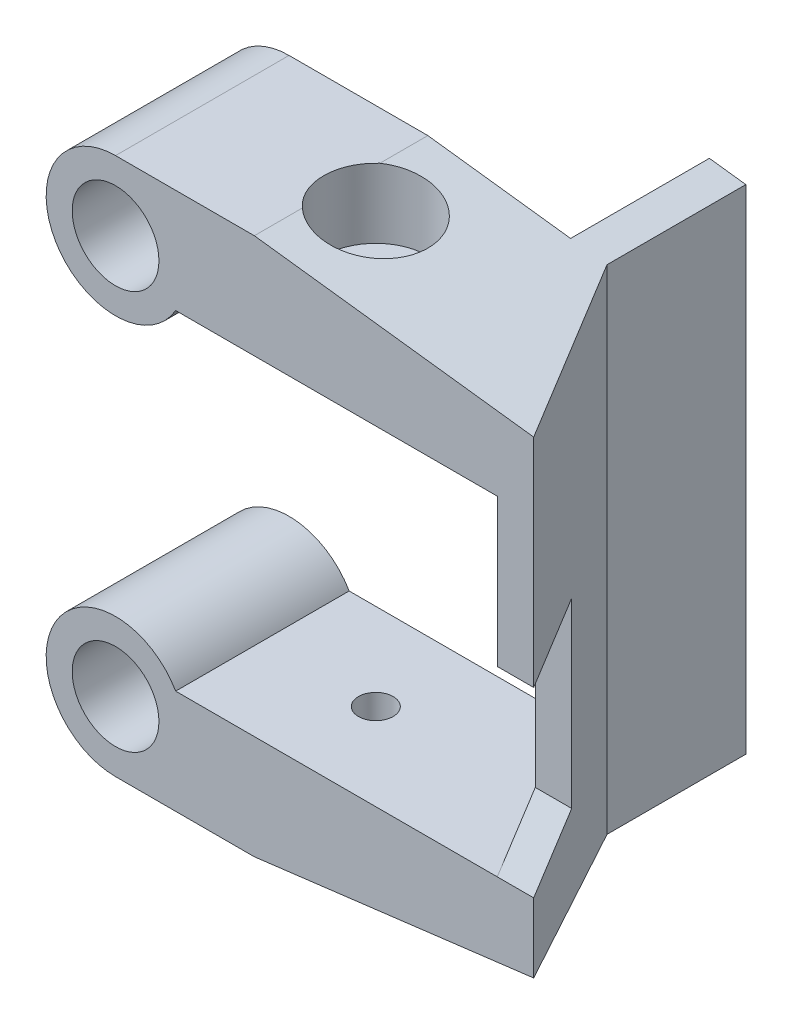
SolidWorks part; units mm, degrees
ref_plane "Alzado" through (0, 0, 0) normal (0, 0, 1) x (1, 0, 0)
ref_plane "Planta" through (0, 0, 0) normal (0, 1, 0) x (1, 0, 0)
ref_plane "Vista lateral" through (0, 0, 0) normal (1, 0, 0) x (0, 0, -1)
sketch "Croquis1" plane through (0, 0, 0) normal (0, 0, 1) x (1, 0, 0)
  line L0 (0, 2.5) -> (0, 3.5) construction
  line L1 (0, 3.5) -> (1.9365, 3.5) construction
  line L2 (3.4641, 3.5) -> (22, 3.5)
  line L3 (22, 3.5) -> (22, -0.5)
  line L4 (22, -0.5) -> (6, -0.5)
  line L7 (22, 3.5) -> (22, 22.5) construction
  line L8 (22, 22.5) -> (-6, 22.5) construction
  line L9 (0, 3.5) -> (0, 1.5) construction
  line L10 (0, -2.5) -> (6, -2.5)
  line L11 (6, -2.5) -> (6, -0.5)
  circle A3 centre (0, 1.5) radius 2.5
  arc A4 (3.4641, 3.5) -> (0, -2.5) centre (0, 1.5) ccw
  dimension "D1" = 6
  dimension "D2" = 2
  dimension "D7" = 5
  dimension "D8" = 4
  dimension "D3" = 1
  dimension "D4" = 22
  dimension "D5" = 4
  dimension "D6" = 19
extrude "Saliente-Extruir1" add sketch "Croquis1" along normal blind 10
sketch "Croquis2" plane through (0, -0.5, 0) normal (0, -1, 0) x (1, 0, 0)
  line L0 (22, 10) -> (16.2265, 0)
  line L1 (6, 0) -> (22, 0) construction
  line L2 (16.2265, 0) -> (22, 0)
  line L3 (22, 0) -> (22, 10)
  circle A0 centre (10, 5) radius 1
  dimension "D2" = 12
  dimension "D1" = 30
extrude "Cortar-Extruir1" cut sketch "Croquis2" against normal up to vertex (4 mm away) up to point (3.4641, 3.5, 10)
sketch "Croquis3" plane through (0, -0.5, 0) normal (0, -1, 0) x (1, 0, 0)
  circle A0 centre (10, 5) radius 3
  dimension "D1" = 6
extrude "Cortar-Extruir2" cut sketch "Croquis3" against normal blind 2
sketch "Croquis4" plane through (0, -0.5, 0) normal (0, -1, 0) x (1, 0, 0)
  line L0 (22, 10) -> (24.1, 10)
  line L1 (24.1, 10) -> (18.3265, 0)
  line L2 (18.3265, 0) -> (16.2265, 0)
  line L3 (22, 10) -> (16.2265, 0)
  dimension "D1" = 2.1
  dimension "D2" = 2.1
extrude "Saliente-Extruir2" add sketch "Croquis4" against normal blind 13.5
sketch "Croquis6" plane through (0, -0.5, 0) normal (0, -1, 0) x (1, 0, 0)
  line L0 (6, 10) -> (6, 0)
  line L1 (6, 0) -> (18.3265, 0)
  line L2 (18.3265, 0) -> (24.1, 10)
  line L3 (24.1, 10) -> (6, 10)
  circle A0 centre (10, 5) radius 3
extrude "Saliente-Extruir3" add sketch "Croquis6" along normal up to vertex (2 mm away) up to point (6, -2.5, 0)
sketch "Croquis7" plane through (0, 0, 10) normal (0, 0, 1) x (1, 0, 0)
  line L0 (22, 3.5) -> (22, -0.5) construction
  line L1 (22, -0.5) -> (24.1, -0.5) construction
  line L2 (24.1, 13) -> (24.1, -2.5) construction
  line L3 (24.1, -0.5) -> (8, -2.5)
  line L4 (0, -2.5) -> (24.1, -2.5) construction
  line L5 (8, -2.5) -> (24.1, -2.5)
  line L6 (24.1, -2.5) -> (24.1, -0.5)
  dimension "D1" = 8
extrude "Cortar-Extruir3" cut sketch "Croquis7" against normal up to vertex (10 mm away) up to point (0, -2.5, 0)
sketch "Croquis8" plane through (0, 0, 0) normal (0, 0, -1) x (-1, 0, 0)
  line L0 (-16.2265, 13) -> (-18.3265, 13)
  line L1 (-18.3265, 13) -> (-18.3265, -1.2172)
  line L2 (-18.3265, -1.2172) -> (-16.2265, -1.4781)
  line L3 (-18.3265, -1.2172) -> (-8, -2.5) construction
  line L4 (-16.2265, -1.4781) -> (-16.2265, 13)
extrude "Saliente-Extruir4" add sketch "Croquis8" along normal blind 8
mirror "Simetría1" about plane through (0, 13, 0) normal (0, 1, 0) of bodies 107
sketch "Croquis9" plane through (0, 0, 10) normal (0, 0, 1) x (1, 0, 0)
  line L0 (24.1, 26.5) -> (24.1, -0.5) construction
  line L1 (22, 3.5) -> (24.1, 3.5)
  line L2 (22, 3.5) -> (22, 14)
  line L3 (22, 14) -> (24.1, 14)
  line L4 (24.1, 3.5) -> (24.1, 14)
  dimension "D1" = 10.5
extrude "Cortar-Extruir4" cut sketch "Croquis9" along direction (0.499, -0.062, 0.8644) on the side against the normal blind 6
sketch "Croquis10" plane through (0, -2.5, 0) normal (0, -1, 0) x (1, 0, 0)
  text T0 "30º"
  point P1 (0, 0)
  point P2 (0.1562, 3.541)
  point P3 (0.1727, 4.8053)
  point P4 (0.1761, 5.2794)
extrude "Cortar-Extruir5" cut sketch "Croquis10" against normal blind 1
